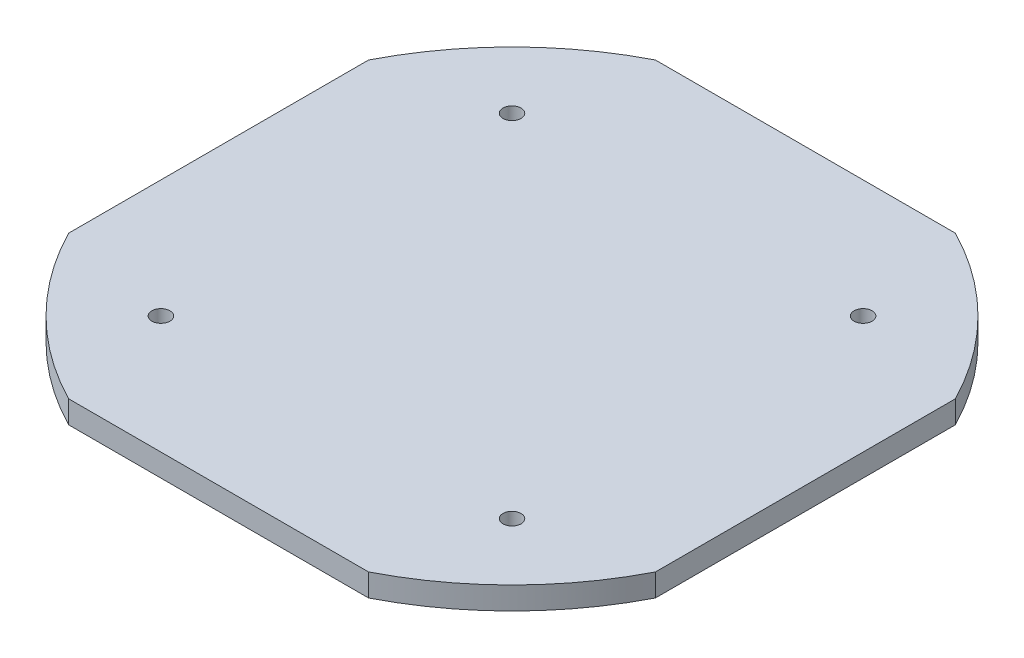
SolidWorks part; units mm, degrees
ref_plane "Front Plane" through (0, 0, 0) normal (0, 0, 1) x (1, 0, 0)
ref_plane "Top Plane" through (0, 0, 0) normal (0, 1, 0) x (1, 0, 0)
ref_plane "Right Plane" through (0, 0, 0) normal (1, 0, 0) x (0, 0, -1)
sketch "Sketch1" plane through (0, 0, 0) normal (0, 1, 0) x (1, 0, 0)
  line L0 (65, 33.2265) -> (65, -33.2265)
  line L1 (65, 33.2265) -> (0, 0) construction
  line L2 (0, 0) -> (65, -33.2265) construction
  line L3 (33.2265, -65) -> (0, 0) construction
  line L4 (0, 0) -> (-33.2265, -65) construction
  line L5 (33.2265, -65) -> (-33.2265, -65)
  line L6 (-65, -33.2265) -> (0, 0) construction
  line L7 (0, 0) -> (-65, 33.2265) construction
  line L8 (-65, -33.2265) -> (-65, 33.2265)
  line L9 (-33.2265, 65) -> (0, 0) construction
  line L10 (0, 0) -> (33.2265, 65) construction
  line L11 (-33.2265, 65) -> (33.2265, 65)
  arc A0 (-65, -33.2265) -> (-33.2265, -65) centre (0, 0) ccw
  arc A1 (-65, 33.2265) -> (-65, -33.2265) centre (0, 0) ccw construction
  arc A2 (33.2265, 65) -> (-33.2265, 65) centre (0, 0) ccw construction
  arc A3 (-33.2265, 65) -> (-65, 33.2265) centre (0, 0) ccw
  arc A4 (65, -33.2265) -> (65, 33.2265) centre (0, 0) ccw construction
  arc A5 (65, 33.2265) -> (33.2265, 65) centre (0, 0) ccw
  arc A6 (-33.2265, -65) -> (33.2265, -65) centre (0, 0) ccw construction
  arc A7 (33.2265, -65) -> (65, -33.2265) centre (0, 0) ccw
  point P14 (0, 0)
  dimension "D1" = 146
  dimension "D2" = 65
  dimension "D3" = 4
extrude "Boss-Extrude1" add sketch "Sketch1" along normal blind 5
sketch "Sketch2" plane through (0, 5, 0) normal (0, 1, 0) x (1, 0, 0)
  point P0 (37.7109, 0)
  point P2 (0, 39.9735)
  point P4 (-38.2765, 0)
  point P6 (0, -34.694)
sketch "Sketch5" plane through (0, 5, 0) normal (0, 1, 0) x (1, 0, 0)
  line L0 (38.8909, 38.8909) -> (0, 0) construction
  line L1 (0, 0) -> (-38.8909, -38.8909) construction
  line L3 (-38.8909, 38.8909) -> (0, 0) construction
  line L4 (0, 0) -> (38.8909, -38.8909) construction
  line L5 (0, 0) -> (0, 65) construction
  line L6 (33.2265, 65) -> (-33.2265, 65) construction
  point P0 (38.8909, 38.8909)
  point P3 (38.8909, -38.8909)
  point P5 (-38.8909, -38.8909)
  point P7 (-38.8909, 38.8909)
  dimension "D1" = 45
  dimension "D2" = 55
hole_wizard "Ø4.0mm Dowel Hole2" positions "Sketch5" profile "Sketch6" hole size "Ø4.0" standard "ISO" end condition through all
sketch "Sketch6" plane through (38.8909, 5, -38.8909) normal (1, 0, 0) x (0, 0, 1)
  line L0 (0, 0) -> (0, 5)
  line L1 (0, 5) -> (2, 5)
  line L2 (2, 5) -> (2, 0)
  line L5 (2, 0) -> (0, 0)
  line L11 (0, -6.35) -> (0, 107.95) construction
  dimension "Thru Hole Dia." = 4
  dimension "Thru Hole Depth" = 5
sketch "Sketch7" plane through (0, 0, 0) normal (0, -1, 0) x (1, 0, 0)
  line L0 (38.85, -20.1) -> (-38.85, -20.1) construction
  line L1 (-38.85, 20.1) -> (38.85, 20.1) construction
  circle A0 centre (27.8, -9.75) radius 1.7 construction
  circle A1 centre (27.8, 9.75) radius 1.7 construction
  circle A2 centre (-27.8, 9.75) radius 1.7 construction
  circle A3 centre (-27.8, -9.75) radius 1.7 construction
  point P12 (0, 0)
  point P13 (0, 0)
sketch "Sketch8" plane through (0, 5, 0) normal (0, 1, 0) x (1, 0, 0)
  circle A0 centre (0, 0) radius 10 construction
  point P3 (0, 0)
  dimension "D1" = 20
